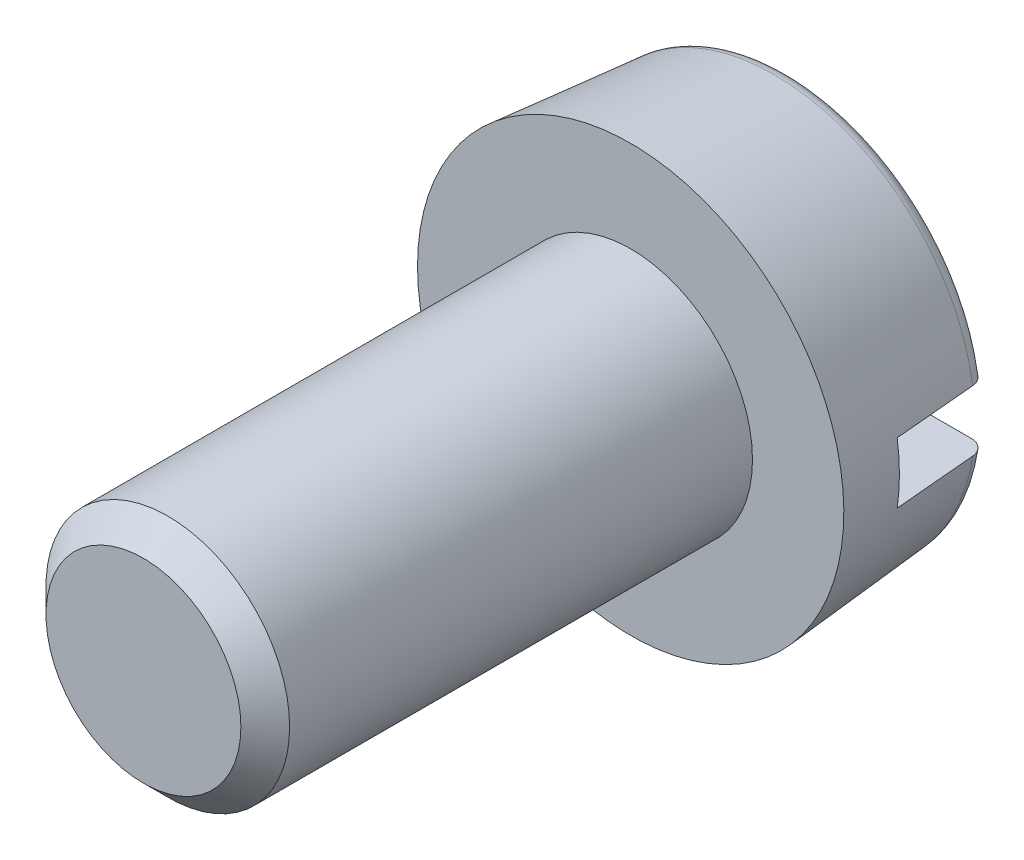
SolidWorks part; units mm, degrees
material "Acier allié"
ref_plane "Plan1" through (0, 0, 0) normal (0, 0, 1) x (1, 0, 0)
ref_plane "Plan2" through (0, 0, 0) normal (0, 1, 0) x (1, 0, 0)
ref_plane "Plan3" through (0, 0, 0) normal (1, 0, 0) x (0, 0, -1)
ref_axis "Z Axis" through (0, 0, -50) along (0, 0, 1)
sketch "Esquisse1" plane through (0, 0, 0) normal (0, 1, 0) x (1, 0, 0)
  line L0 (0, 0) -> (0, 2.6) construction
  line L1 (0, 0) -> (3.5, 0)
  line L2 (0, 0) -> (0, 2.6)
  line L3 (0, 2.6) -> (3.0343, 2.6)
  line L5 (3.5, 0) -> (3.2933, 2.3627)
  arc A0 (3.0343, 2.6) -> (3.2933, 2.3627) centre (3.0343, 2.34) cw
  dimension "D3" = 0.26
  dimension "D1" = 3.5
  dimension "D2" = 2.6
  dimension "D4" = 5
revolve "Base-Révolution" add sketch "Esquisse1" angle 360 about L0 reverse direction yes
sketch "Esquisse2" plane through (0, 0, -2.6) normal (0, 0, 1) x (1, 0, 0)
  line L1 (-3.5, 0.5) -> (3.5, 0.5)
  line L2 (-3.5, 0.5) -> (-3.5, -0.5)
  line L3 (-3.5, -0.5) -> (3.5, -0.5)
  line L4 (3.5, 0.5) -> (3.5, -0.5)
  circle A0 centre (0, 0) radius 3.5 construction
extrude "Enlev. mat.-Extru.1" cut sketch "Esquisse2" along normal blind 1.6
sketch "Esquisse3" plane through (0, 0, 0) normal (0, 1, 0) x (1, 0, 0)
  line L1 (0, 0) -> (0, -8) construction
  line L2 (0, 0) -> (2, 0)
  line L3 (0, 0) -> (0, -8)
  line L4 (0, -8) -> (2, -8)
  line L6 (2, 0) -> (2, -8)
  dimension "D1" = 8
  dimension "D2" = 2
revolve "Boss.-Révol.1" add sketch "Esquisse3"
cosmetic thread "Représentation de filetage1" [suppressed]
chamfer "Chanfrein1" distance 0.4 angle 45 1 edges at (2, 0, 8)
sketch "Esquisse4" plane through (0, 0, 0) normal (0, 1, 0) x (1, 0, 0)
  line L0 (1.573, -8.0427) -> (1.573, -7.9573)
  line L2 (1.573, -7.9573) -> (2.0427, -7.6861)
  line L3 (1.573, -8.0427) -> (2.0427, -8.3139)
  line L4 (2.0427, -7.6861) -> (2.0427, -8.3139)
  line L6 (2, 0) -> (2, -8) construction
  line L7 (0, -8) -> (2, -8) construction
  point P4 (2, -8)
  dimension "D2" = 0.0427
  dimension "D3" = 0.0427
  dimension "D4" = 0.4697
  dimension "D5" = 60
  dimension "D1" = 0.427
  dimension "D6" = 60
sketch "Esquisse5" plane through (0, 0, 8) normal (0, 0, 1) x (1, 0, 0)
  circle A0 centre (0, 0) radius 2 construction
  circle A1 centre (0, 0) radius 2
curve "Hélice1" pitch 0.7 height 9.72 turns 13.8857
sweep "Enlèvement de matière-Balayage1" [suppressed] cut profiles "Esquisse4" path "Hélice1"
equation "\"D3@Esquisse1\"=\"D2@Esquisse1\"/10"
equation "\"D1@Chanfrein1\"=\"D2@Esquisse3\"*0.2"
equation "\"D3@Esquisse4\"=0.1*\"D1@Esquisse4\""
equation "\"D4@Esquisse4\"=1.1*\"D1@Esquisse4\""
equation "\"D2@Esquisse4\"=0.1*\"D1@Esquisse4\""
equation "\"D1@Esquisse4\"=0.61*\"D4@Hélice1\""
equation "\"D1@Représentation de filetage1\"=\"D3@Hélice1\""
equation "\"D2@Représentation de filetage1\"=\"D2@Esquisse3\"*1.6"
